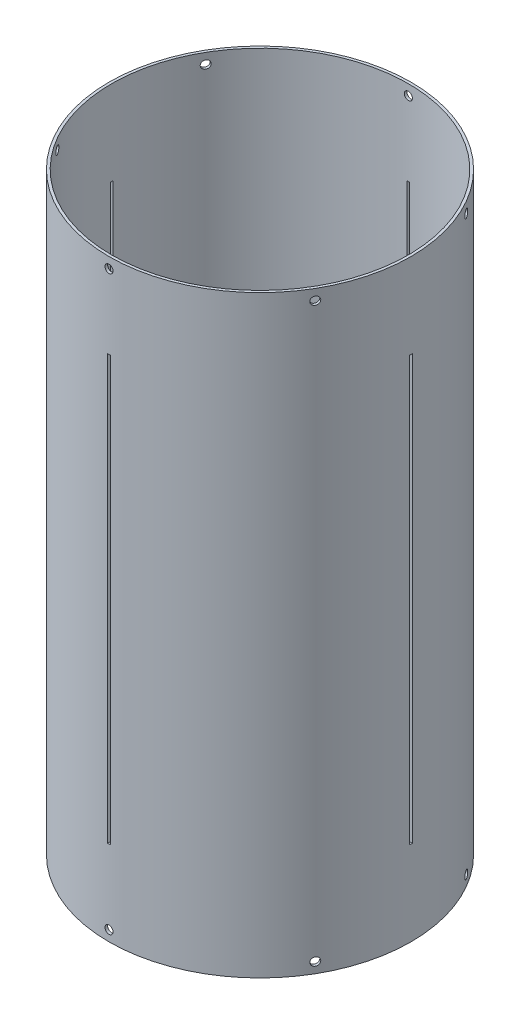
SolidWorks part; units mm, degrees
material "A-Glass Fiber"
ref_plane "Front Plane" through (0, 0, 0) normal (0, 0, 1) x (1, 0, 0)
ref_plane "Top Plane" through (0, 0, 0) normal (0, 1, 0) x (1, 0, 0)
ref_plane "Right Plane" through (0, 0, 0) normal (1, 0, 0) x (0, 0, -1)
sketch "Sketch2" plane through (0, 0, 0) normal (0, 1, 0) x (1, 0, 0)
  circle A0 centre (0, 0) radius 88.9
  circle A1 centre (0, 0) radius 90.4875
  dimension "D1" = 177.8
  dimension "D2" = 1.5875
extrude "Boss-Extrude1" add sketch "Sketch2" along normal blind 355.6
sketch "Sketch3" plane through (0, 0, 0) normal (0, 0, 1) x (1, 0, 0)
  line L0 (0, 0) -> (0, 6.35) construction
  line L1 (-90.4875, 0) -> (90.4875, 0) construction
  line L2 (-90.4875, 0) -> (-90.4875, 355.6) construction
  line L3 (-90.4875, 355.6) -> (90.4875, 355.6) construction
  line L4 (90.4875, 0) -> (90.4875, 355.6) construction
  line L5 (0, 6.35) -> (0, 349.25) construction
  line L7 (0, 355.6) -> (0, 349.25) construction
  circle A0 centre (0, 349.25) radius 2.413
  circle A1 centre (0, 6.35) radius 2.413
  dimension "D2" = 4.826
  dimension "D4" = 4.826
  dimension "D1" = 6.35
  dimension "D3" = 6.35
extrude "Cut-Extrude1" cut sketch "Sketch3" against normal through all both and the other way through all
pattern_circular "CirPattern1" count 6 over 360 about axis through (0, 355.6, 0) along (0, 1, 0) of "Cut-Extrude1"
ref_plane "Plane1" through (-90.4875, 0, 0) normal (-1, 0, 0) x (0, 0, 1)
sketch "Sketch4" plane through (-90.4875, 0, 0) normal (-1, 0, 0) x (0, 0, 1)
  line L0 (0, 0) -> (0, 355.6) construction
  line L2 (-0.7937, 50.8) -> (0.7937, 50.8)
  line L3 (-0.7937, 50.8) -> (-0.7937, 304.8)
  line L4 (-0.7937, 304.8) -> (0.7937, 304.8)
  line L5 (0.7937, 50.8) -> (0.7937, 304.8)
  line L6 (-0.7937, 50.8) -> (0.7937, 304.8) construction
  line L7 (-0.7937, 304.8) -> (0.7937, 50.8) construction
  point P3 (0, 177.8)
  dimension "D1" = 355.6
  dimension "D2" = 1.5875
  dimension "D3" = 254
extrude "Cut-Extrude2" cut sketch "Sketch4" against normal blind 2.54
pattern_circular "CirPattern2" count 4 over 360 about axis through (0, 355.6, 0) along (0, 1, 0) of "Cut-Extrude2"
